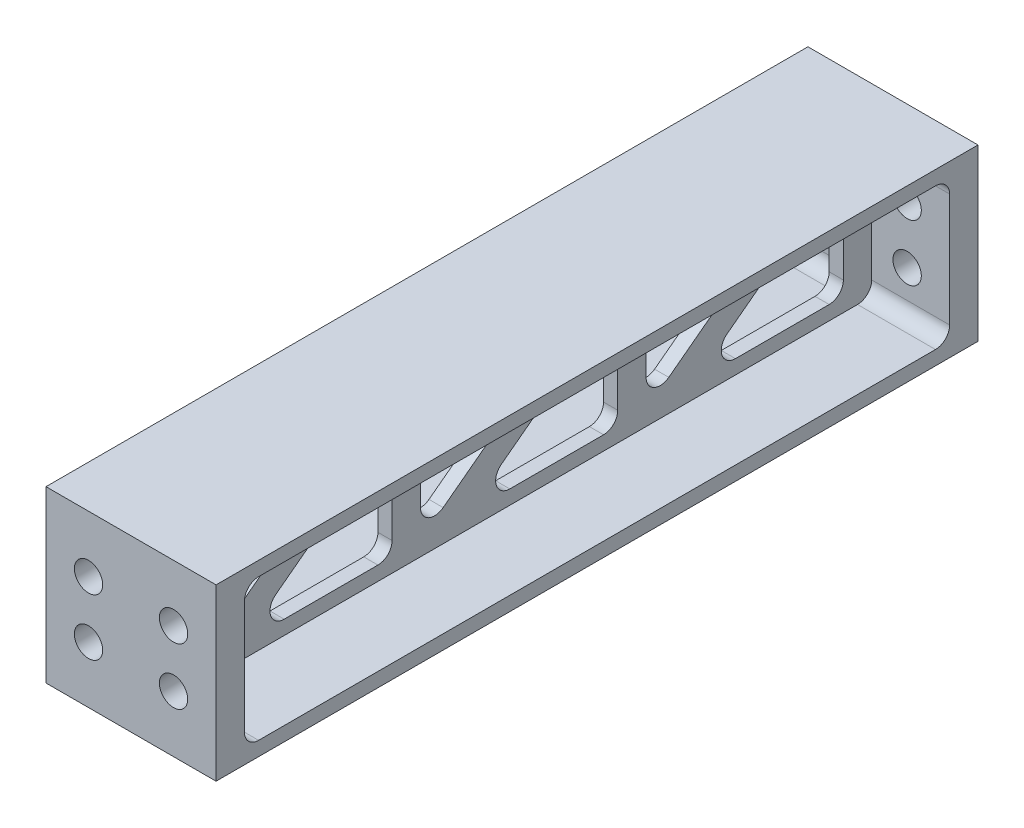
SolidWorks part; units mm, degrees
material "6061 Alloy"
ref_plane "Front Plane" through (0, 0, 0) normal (0, 0, 1) x (1, 0, 0)
ref_plane "Top Plane" through (0, 0, 0) normal (0, 1, 0) x (1, 0, 0)
ref_plane "Right Plane" through (0, 0, 0) normal (1, 0, 0) x (0, 0, -1)
sketch "Sketch2" plane through (0, 0, 0) normal (0, 0, 1) x (1, 0, 0)
  line L1 (0, 0) -> (38.1, 0)
  line L2 (0, 0) -> (0, 38.1)
  line L3 (0, 38.1) -> (38.1, 38.1)
  line L4 (38.1, 0) -> (38.1, 38.1)
  dimension "D1" = 38.1
extrude "Boss-Extrude1" add sketch "Sketch2" along normal up to surface (170.686 mm away)
ref_plane "Plane1" through (19.05, 0, 0) normal (1, 0, 0) x (0, 0, -1)
sketch "Sketch3" plane through (38.1, 0, 0) normal (1, 0, 0) x (0, 0, -1)
  line L4 (-85.343, 34.925) -> (-85.343, 38.1) construction
  line L5 (-164.336, 34.925) -> (-6.35, 34.925)
  line L6 (-164.336, 34.925) -> (-164.336, 3.175)
  line L7 (-164.336, 3.175) -> (-6.35, 3.175)
  line L8 (-6.35, 34.925) -> (-6.35, 3.175)
  line L9 (-170.686, 38.1) -> (0, 38.1) construction
  line L10 (-6.35, 19.05) -> (0, 19.05) construction
  line L11 (0, 0) -> (0, 38.1) construction
  dimension "D1" = 6.35
  dimension "D2" = 3.175
extrude "Cut-Extrude1" cut sketch "Sketch3" against normal blind 17.4625
fillet "Fillet1" radius 3.175 4 edges at (29.3688, 3.175, 6.35) (29.3688, 3.175, 164.336) (29.3688, 34.925, 164.336) (29.3688, 34.925, 6.35)
mirror "Mirror1" about plane through (19.05, 0, 0) normal (1, 0, 0) of "Fillet1", "Cut-Extrude1"
hole_wizard "1/4 (0.25) Diameter Hole1" positions "Sketch5" profile "Sketch6" hole size "1/4" standard "ANSI Inch" end condition through all
sketch "Sketch5" plane through (0, 0, 0) normal (0, 0, -1) x (-1, 0, 0)
  line L0 (0, 38.1) -> (0, 0) construction
  line L1 (-38.1, 0) -> (-38.1, 38.1) construction
  line L2 (-38.1, 38.1) -> (0, 38.1) construction
  line L3 (0, 0) -> (-38.1, 0) construction
  point P0 (-9.525, 25.4)
  point P2 (-9.525, 12.7)
  point P4 (-28.575, 12.7)
  point P6 (-28.575, 25.4)
  dimension "D1" = 9.525
  dimension "D2" = 9.525
  dimension "D3" = 12.7
  dimension "D4" = 12.7
sketch "Sketch6" plane through (9.525, 25.4, 0) normal (1, 0, 0) x (0, 1, 0)
  line L0 (0, 0) -> (0, 170.686)
  line L1 (0, 170.686) -> (3.175, 170.686)
  line L2 (3.175, 170.686) -> (3.175, 0)
  line L5 (3.175, 0) -> (0, 0)
  line L11 (0, -6.35) -> (0, 107.95) construction
  dimension "Thru Hole Dia." = 6.35
  dimension "Thru Hole Depth" = 170.686
sketch "Sketch7" plane through (17.4625, 0, 0) normal (-1, 0, 0) x (0, 0, 1)
  line L0 (12.7, 31.75) -> (12.7, 6.35)
  line L1 (29.5272, 19.05) -> (33.3525, 24.1185) construction
  line L2 (12.7, 6.35) -> (46.3544, 6.35)
  line L3 (113.7907, 19.05) -> (107.4407, 19.05) construction
  line L4 (63.2453, 19.05) -> (56.8953, 19.05) construction
  line L5 (46.3544, 6.35) -> (12.7, 31.75)
  line L6 (12.7, 19.05) -> (6.35, 19.05) construction
  line L7 (6.35, 6.35) -> (6.35, 31.75) construction
  line L8 (23.2409, 31.75) -> (56.8953, 6.35)
  line L9 (56.8953, 6.35) -> (56.8953, 31.75)
  line L10 (56.8953, 31.75) -> (23.2409, 31.75)
  line L11 (63.2453, 31.75) -> (63.2453, 6.35)
  line L12 (96.8998, 6.35) -> (63.2453, 31.75)
  line L13 (63.2453, 6.35) -> (96.8998, 6.35)
  line L14 (80.0725, 19.05) -> (83.8979, 24.1185) construction
  line L15 (73.7863, 31.75) -> (107.4407, 6.35)
  line L16 (107.4407, 31.75) -> (73.7863, 31.75)
  line L17 (107.4407, 6.35) -> (107.4407, 31.75)
  line L18 (113.7907, 31.75) -> (113.7907, 6.35)
  line L19 (147.4451, 6.35) -> (113.7907, 31.75)
  line L20 (113.7907, 6.35) -> (147.4451, 6.35)
  line L21 (130.6179, 19.05) -> (134.4432, 24.1185) construction
  line L22 (124.3316, 31.75) -> (157.986, 6.35)
  line L23 (157.986, 31.75) -> (124.3316, 31.75)
  line L24 (157.986, 6.35) -> (157.986, 31.75)
  line L25 (157.986, 19.05) -> (164.336, 19.05) construction
  line L26 (164.336, 31.75) -> (164.336, 6.35) construction
  dimension "D1" = 25.4
  dimension "D2" = 6.35
  dimension "D3" = 3
extrude "Cut-Extrude2" cut sketch "Sketch7" against normal up to next
fillet "Fillet3" radius 3.175 18 edges at (19.05, 6.35, 46.3544) (19.05, 6.35, 96.8998) (19.05, 6.35, 147.4451) (19.05, 6.35, 157.986) (19.05, 6.35, 107.4407) (19.05, 6.35, 56.8953) (19.05, 6.35, 12.7) (19.05, 6.35, 63.2453) (19.05, 6.35, 113.7907) (19.05, 31.75, 124.3316) (19.05, 31.75, 73.7863) (19.05, 31.75, 23.2409) (19.05, 31.75, 56.8953) (19.05, 31.75, 107.4407) (19.05, 31.75, 157.986) (19.05, 31.75, 12.7) (19.05, 31.75, 63.2453) (19.05, 31.75, 113.7907)
